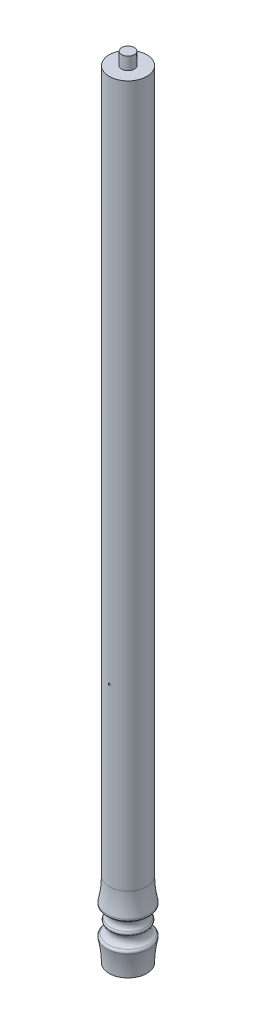
SolidWorks part; units mm, degrees
ref_plane "Front Plane" through (0, 0, 0) normal (0, 0, 1) x (1, 0, 0)
ref_plane "Top Plane" through (0, 0, 0) normal (0, 1, 0) x (1, 0, 0)
ref_plane "Right Plane" through (0, 0, 0) normal (1, 0, 0) x (0, 0, -1)
ref_plane "Plane3" through (0, 787.4, 0) normal (0, 1, 0) x (1, 0, 0)
ref_plane "Plane4" through (0, 800.1, 0) normal (0, 1, 0) x (1, 0, 0)
ref_plane "Plane5" through (0, 165.1, 0) normal (0, 1, 0) x (1, 0, 0)
ref_plane "Plane6" through (0, 203.2, 0) normal (0, 1, 0) x (1, 0, 0)
ref_plane "Plane7" through (0, 254, 0) normal (0, 1, 0) x (1, 0, 0)
ref_plane "Plane8" through (0, 25.4, 0) normal (0, 1, 0) x (1, 0, 0)
ref_plane "Plane9" through (0, 38.1, 0) normal (0, 1, 0) x (1, 0, 0)
ref_plane "Plane10" through (0, 50.8, 0) normal (0, 1, 0) x (1, 0, 0)
ref_plane "Plane11" through (0, 76.2, 0) normal (0, 1, 0) x (1, 0, 0)
ref_plane "Plane14" through (6.35, 0, 0) normal (1, 0, 0) x (0, 0, -1)
ref_plane "Plane15" through (15.875, 0, 0) normal (1, 0, 0) x (0, 0, -1)
ref_plane "Plane16" through (19.05, 0, 0) normal (1, 0, 0) x (0, 0, -1)
ref_plane "Plane17" through (22.225, 0, 0) normal (1, 0, 0) x (0, 0, -1)
sketch "center" plane through (0, 0, 0) normal (0, 0, 1) x (1, 0, 0)
  line L0 (0, 0) -> (0, 787.4)
  line L7 (154.1749, 787.4) -> (-154.1749, 787.4) construction
  line L13 (0, -76.5499) -> (0, 76.5499) construction
ref_axis "Axis1" through (0, -55, 0) along (0, 1, 0)
sketch "Sketch5" plane through (0, 25.4, 0) normal (0, 1, 0) x (1, 0, 0)
  line L0 (22.225, -76.5499) -> (22.225, 76.5499) construction
  circle A0 centre (0, 0) radius 22.225
ref_plane "Plane18" through (0, 31.75, 0) normal (0, 1, 0) x (1, 0, 0)
ref_plane "Plane19" through (0, 44.45, 0) normal (0, 1, 0) x (1, 0, 0)
sketch "Sketch6" plane through (0, 31.75, 0) normal (0, 1, 0) x (1, 0, 0)
  line L0 (15.875, -76.5499) -> (15.875, 76.5499) construction
  circle A0 centre (0, 0) radius 15.875
sketch "Sketch7" plane through (0, 38.1, 0) normal (0, 1, 0) x (1, 0, 0)
  circle A0 centre (0, 0) radius 18.9864
sketch "Sketch8" plane through (0, 44.45, 0) normal (0, 1, 0) x (1, 0, 0)
  circle A0 centre (0, 0) radius 15.875
sketch "Sketch9" plane through (0, 50.8, 0) normal (0, 1, 0) x (1, 0, 0)
  circle A0 centre (0, 0) radius 22.225
sketch "Sketch10" plane through (0, 76.2, 0) normal (0, 1, 0) x (1, 0, 0)
  circle A0 centre (0, 0) radius 18.9864
sketch "Sketch11" plane through (0, 0, 0) normal (0, 1, 0) x (1, 0, 0)
  circle A0 centre (0, 0) radius 18.9864
sketch "revolve sketch" plane through (0, 0, 0) normal (0, 0, 1) x (1, 0, 0)
  line L0 (0, 0) -> (19.05, 0)
  line L1 (18.9864, 0) -> (-18.9864, 0) construction
  line L2 (15.875, -76.5499) -> (15.875, 76.5499) construction
  line L3 (22.225, 25.4) -> (-22.225, 25.4) construction
  line L4 (22.225, -76.5499) -> (22.225, 76.5499) construction
  line L5 (154.1749, 25.4) -> (-154.1749, 25.4) construction
  line L6 (15.875, 31.75) -> (-15.875, 31.75) construction
  line L7 (154.1749, 31.75) -> (-154.1749, 31.75) construction
  line L8 (154.1749, 38.1) -> (-154.1749, 38.1) construction
  line L9 (15.875, 44.45) -> (-15.875, 44.45) construction
  line L10 (154.1749, 44.45) -> (-154.1749, 44.45) construction
  line L11 (22.225, 50.8) -> (-22.225, 50.8) construction
  line L12 (154.1749, 50.8) -> (-154.1749, 50.8) construction
  line L17 (19.05, -76.5499) -> (19.05, 76.5499) construction
  line L18 (154.1749, 0) -> (-154.1749, 0) construction
  line L19 (18.9864, 76.2) -> (-18.9864, 76.2) construction
  line L20 (154.1749, 76.2) -> (-154.1749, 76.2) construction
  line L21 (19.05, 76.2) -> (19.05, 787.4)
  line L22 (154.1749, 787.4) -> (-154.1749, 787.4) construction
  line L23 (19.05, 787.4) -> (6.35, 787.4)
  line L24 (6.35, -76.5499) -> (6.35, 76.5499) construction
  line L25 (6.35, 787.4) -> (6.35, 800.1)
  line L26 (152.7724, 800.1) -> (-152.7724, 800.1) construction
  line L27 (6.35, 800.1) -> (0, 800.1)
  line L28 (0, -76.5499) -> (0, 76.5499) construction
  line L29 (0, 800.1) -> (0, 0)
  arc A0 (19.05, 0) -> (21.6122, 22.8517) centre (122.2375, 0) cw
  arc A1 (15.875, 31.75) -> (20.018, 25.7959) centre (22.225, 31.75) ccw
  arc A2 (15.875, 31.75) -> (17.7809, 36.2857) centre (22.225, 31.75) cw
  arc A3 (17.7809, 39.9143) -> (15.875, 44.45) centre (22.225, 44.45) cw
  arc A4 (15.875, 44.45) -> (20.018, 50.4041) centre (22.225, 44.45) cw
  arc A5 (21.6122, 53.3483) -> (19.05, 76.2) centre (122.2375, 76.2) cw
  arc A6 (17.7809, 36.2857) -> (17.7809, 39.9143) centre (16.0033, 38.1) ccw
  arc A7 (21.6122, 22.8517) -> (20.018, 25.7959) centre (19.1352, 23.4142) ccw
  arc A8 (20.018, 50.4041) -> (21.6122, 53.3483) centre (19.1352, 52.7858) ccw
  point P49 (22.225, 38.1)
  point P52 (22.225, 25.4)
  point P55 (22.225, 50.8)
  point P60 (22.225, 25.4)
  point P62 (22.225, 50.8)
  dimension "D1" = 2.54
  dimension "D2" = 2.54
  dimension "D3" = 2.54
revolve "Revolve1" add sketch "revolve sketch" angle 360 about axis through (0, -55, 0) along (0, 1, 0)
ref_plane "Plane20" through (0, 317.5, 0) normal (0, 1, 0) x (1, 0, 0)
ref_axis "Axis2" through (162.1372, 317.5, 0) along (-1, 0, 0)
ref_axis "Axis3" through (0, 254, -88.99) along (0, 0, 1)
ref_axis "Axis4" through (0, 203.2, -88.99) along (0, 0, 1)
ref_axis "Axis5" through (0, 165.1, -88.99) along (0, 0, 1)
ref_plane "Plane21" through (0, 0, 6.35) normal (0, 0, 1) x (1, 0, 0)
ref_plane "Plane22" through (0, 0, 19.05) normal (0, 0, 1) x (1, 0, 0)
sketch "Sketch15" plane through (0, 0, 19.05) normal (0, 0, 1) x (1, 0, 0)
  line L0 (0, 0) -> (0, 787.4) construction
  line L1 (142.5044, 254) -> (-142.5044, 254) construction
  circle A0 centre (0, 254) radius 0.9922
  dimension "D1" = 1.9844
extrude "Cut-Extrude1" cut sketch "Sketch15" against normal up to surface (12.7 mm away) up to plane "Plane21"
sketch "Sketch16" plane through (19.05, 0, 0) normal (1, 0, 0) x (0, 0, -1)
  line L0 (142.5044, 317.5) -> (-142.5044, 317.5) construction
  line L1 (0, 0) -> (0, 787.4) construction
  circle A0 centre (0, 317.5) radius 0.9922
  dimension "D1" = 1.9844
ref_plane "Plane24" through (-6.35, 0, 0) normal (-1, 0, 0) x (0, 0, 1)
ref_plane "Plane25" through (-19.05, 0, 0) normal (-1, 0, 0) x (0, 0, 1)
sketch "Sketch18" plane through (-19.05, 0, 0) normal (-1, 0, 0) x (0, 0, 1)
  line L0 (0, -143.5378) -> (0, 143.5378) construction
  circle A0 centre (0, 317.5) radius 0.9922
extrude "Cut-Extrude3" cut sketch "Sketch18" against normal up to surface (12.7 mm away) contours A0 up to plane "Plane24"
ref_plane "Plane26" through (0, 0, -19.05) normal (0, 0, -1) x (-1, 0, 0)
